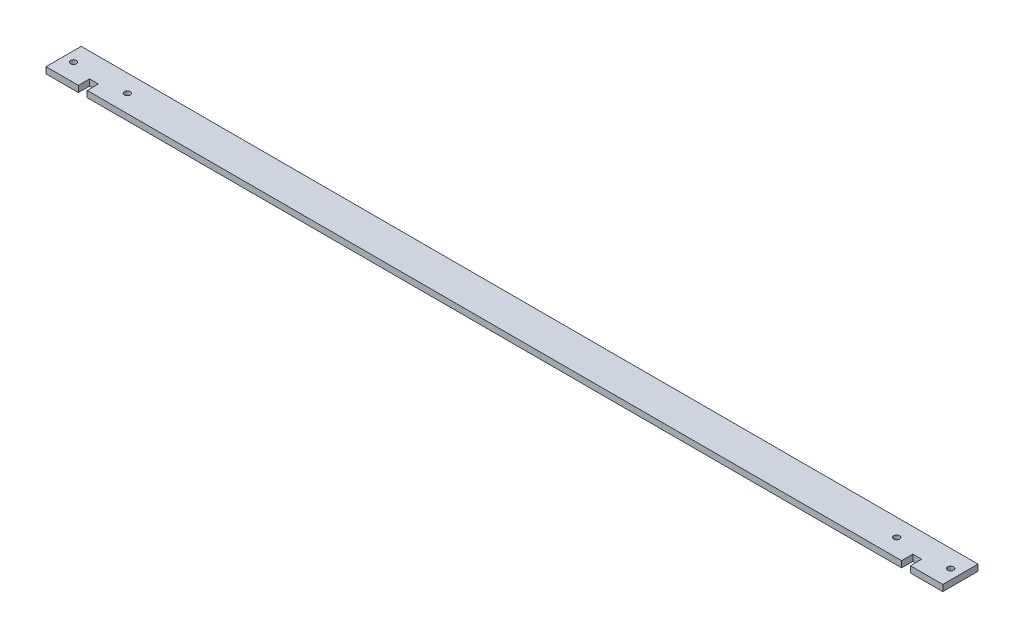
SolidWorks part; units mm, degrees
material "Cedar"
ref_plane "Front Plane" through (0, 0, 0) normal (0, 0, 1) x (1, 0, 0)
ref_plane "Top Plane" through (0, 0, 0) normal (0, 1, 0) x (1, 0, 0)
ref_plane "Right Plane" through (0, 0, 0) normal (1, 0, 0) x (0, 0, -1)
sketch "Sketch1" plane through (0, 0, 0) normal (0, 1, 0) x (1, 0, 0)
  line L1 (457.2, -17.95) -> (-457.2, -17.95)
  line L2 (457.2, -17.95) -> (457.2, 17.95)
  line L3 (457.2, 17.95) -> (-457.2, 17.95)
  line L4 (-457.2, -17.95) -> (-457.2, 17.95)
  line L5 (457.2, -17.95) -> (-457.2, 17.95) construction
  line L6 (457.2, 17.95) -> (-457.2, -17.95) construction
  point P0 (0, 0)
  dimension "D1" = 914.4
  dimension "D2" = 35.9
extrude "Boss-Extrude1" add sketch "Sketch1" along normal blind 6.4
sketch "Sketch2" plane through (0, 6.4, 0) normal (0, 1, 0) x (1, 0, 0)
  line L0 (-424.2, -17.95) -> (-424.2, -6.55)
  line L1 (-457.2, -17.95) -> (457.2, -17.95) construction
  line L2 (-424.2, -6.55) -> (-415.2, -6.55)
  line L3 (-415.2, -6.55) -> (-415.2, -17.95)
  line L4 (-419.7, -17.95) -> (-419.7, -6.55) construction
  line L5 (-422.7, -12.8528) -> (-422.7, -17.95) construction
  line L6 (-416.7, -17.95) -> (-416.7, -12.8528) construction
  line L7 (-422.7, -17.95) -> (-416.7, -17.95) construction
  circle A0 centre (-419.7, -11.05) radius 3 construction
  point P8 (-422.7, -17.95)
  point P9 (0, 0)
  point P12 (-416.7, -17.95)
  point P17 (-419.7, -8.05)
  dimension "D1" = 1.5
  dimension "D2" = 1.5
extrude "Cut-Extrude1" cut sketch "Sketch2" against normal through all and the other way through all flip side to cut
sketch "Sketch3" plane through (0, 6.4, 0) normal (0, 1, 0) x (1, 0, 0)
  circle A0 centre (-447.2, 0.05) radius 3
  circle A1 centre (-447.2, 0.05) radius 3 construction
  circle A2 centre (-392.2, 0.05) radius 3
  circle A3 centre (-392.2, 0.05) radius 3 construction
extrude "Cut-Extrude2" cut sketch "Sketch3" against normal through all
ref_plane "Plane1" through (0, 0, 0) normal (-1, 0, 0) x (0, 0, 1)
mirror "Mirror1" about plane through (0, 0, 0) normal (-1, 0, 0) of "Cut-Extrude2", "Cut-Extrude1"
